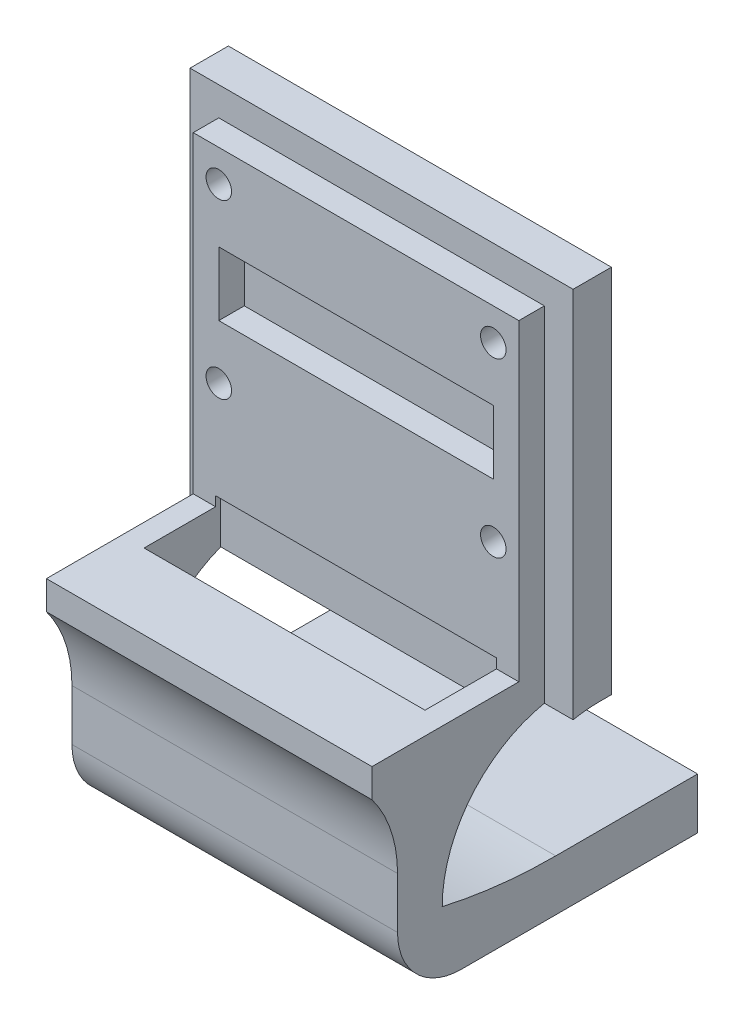
SolidWorks part; units mm, degrees
ref_plane "Alzado" through (0, 0, 0) normal (0, 0, 1) x (1, 0, 0)
ref_plane "Planta" through (0, 0, 0) normal (0, 1, 0) x (1, 0, 0)
ref_plane "Vista lateral" through (0, 0, 0) normal (1, 0, 0) x (0, 0, -1)
sketch "Croquis3" plane through (0, 0, 0) normal (0, 0, 1) x (1, 0, 0)
  line L1 (15, 14.5) -> (-15, 14.5)
  line L2 (15, 14.5) -> (15, -14.5)
  line L3 (15, -14.5) -> (-15, -14.5)
  line L4 (-15, 14.5) -> (-15, -14.5)
  line L5 (15, 14.5) -> (-15, -14.5) construction
  line L6 (15, -14.5) -> (-15, 14.5) construction
  point P0 (0, 0)
  dimension "D1" = 30
  dimension "D2" = 29
extrude "Saliente-Extruir1" add sketch "Croquis3" along normal blind 5
sketch "Croquis5" plane through (0, 0, 5) normal (0, 0, 1) x (1, 0, 0)
  line L0 (15, -14.5) -> (15, 14.5) construction
  line L1 (-15, -14.5) -> (15, -14.5) construction
  line L2 (-15, 14.5) -> (-15, -14.5) construction
  line L3 (15, 14.5) -> (-15, 14.5) construction
  line L4 (15, -14.5) -> (15, 14.5)
  line L5 (-15, -14.5) -> (15, -14.5)
  line L6 (-15, 14.5) -> (-15, -14.5)
  line L7 (15, 14.5) -> (-15, 14.5)
  line L9 (12.75, 12.25) -> (-12.75, 12.25)
  line L10 (12.75, 12.25) -> (12.75, -12.25)
  line L11 (12.75, -12.25) -> (-12.75, -12.25)
  line L12 (-12.75, 12.25) -> (-12.75, -12.25)
  line L13 (12.75, 12.25) -> (-12.75, -12.25) construction
  line L14 (12.75, -12.25) -> (-12.75, 12.25) construction
  point P3 (0, 0)
  dimension "D1" = 25.5
  dimension "D2" = 24.5
extrude "Cortar-Extruir1" cut sketch "Croquis5" against normal blind 2
sketch "Croquis6" plane through (0, 0, 0) normal (0, 0, 1) x (1, 0, 0)
  line L0 (0, 15.8754) -> (0, -15.8754) construction
  line L1 (-12.75, 12.25) -> (-12.75, -12.25) construction
  line L2 (12.75, 12.25) -> (-12.75, 12.25) construction
  line L3 (-10.75, -3.75) -> (10.75, -3.75) construction
  line L4 (10.75, -3.75) -> (10.75, 9.75) construction
  line L5 (10.75, 9.75) -> (-10.75, 9.75) construction
  line L6 (-10.75, 9.75) -> (-10.75, -3.75) construction
  circle A0 centre (-10.75, 9.75) radius 1
  circle A2 centre (-10.75, -3.75) radius 1
  circle A9 centre (10.75, -3.75) radius 1
  circle A10 centre (10.75, 9.75) radius 1
  point P4 (0, 0)
  dimension "D1" = 2
  dimension "D2" = 2
  dimension "D3" = 2.5
  dimension "D4" = 13.5
sketch "Croquis9" plane through (0, 0, 3) normal (0, 0, 1) x (1, 0, 0)
  line L0 (-15, -14.5) -> (15, -14.5) construction
  line L1 (-12.75, -12.25) -> (12.75, -12.25)
  line L2 (-12.75, -12.25) -> (-12.75, -14.5)
  line L3 (-12.75, -14.5) -> (12.75, -14.5)
  line L4 (12.75, -12.25) -> (12.75, -14.5)
  line L5 (12.75, -12.25) -> (12.75, 12.25) construction
extrude "Saliente-Extruir2" add sketch "Croquis9" along normal blind 13.5
sketch "Croquis11" plane through (0, -14.5, 0) normal (0, -1, 0) x (1, 0, 0)
  line L1 (11, 10.6) -> (-11, 10.6)
  line L2 (11, 10.6) -> (11, 4.6)
  line L3 (11, 4.6) -> (-11, 4.6)
  line L4 (-11, 10.6) -> (-11, 4.6)
  line L5 (11, 10.6) -> (-11, 4.6) construction
  line L6 (11, 4.6) -> (-11, 10.6) construction
  line L7 (-15, 3) -> (-12.75, 3) construction
  point P0 (0, 7.6)
  dimension "D1" = 22
  dimension "D2" = 11
  dimension "D3" = 6
  dimension "D4" = 1.6
extrude "Cortar-Extruir3" cut sketch "Croquis11" against normal blind 3
sketch "Croquis12" plane through (0, -14.5, 0) normal (0, -1, 0) x (1, 0, 0)
  line L0 (12.75, 16.5) -> (12.75, 3) construction
  line L1 (12.75, 11) -> (-12.75, 11)
  line L2 (12.75, 11) -> (12.75, 14.5)
  line L3 (12.75, 14.5) -> (-12.75, 14.5)
  line L4 (-12.75, 11) -> (-12.75, 14.5)
  line L5 (-12.75, 16.5) -> (-12.75, 3) construction
  line L7 (-12.75, 16.5) -> (12.75, 16.5) construction
  dimension "D1" = 3.5
  dimension "D2" = 2
extrude "Saliente-Extruir3" add sketch "Croquis12" along normal blind 15
sketch "Croquis13" plane through (0, 0, 11) normal (0, 0, -1) x (-1, 0, 0)
  line L0 (12.75, -29.5) -> (12.75, -14.5) construction
  line L1 (-12.75, -29.5) -> (12.75, -29.5)
  line L2 (-12.75, -29.5) -> (-12.75, -25.5)
  line L3 (-12.75, -25.5) -> (12.75, -25.5)
  line L4 (12.75, -29.5) -> (12.75, -25.5)
  dimension "D1" = 4
extrude "Saliente-Extruir4" add sketch "Croquis13" along normal blind 20
fillet "Redondeo3" radius 5 1 edges at (0, -29.5, 14.5)
sketch "Croquis14" plane through (0, -29.5, 0) normal (0, -1, 0) x (1, 0, 0)
  line L0 (12.75, -9) -> (-12.75, -9) construction
  circle A0 centre (0, -3) radius 1.5
  dimension "D1" = 3
  dimension "D2" = 6
extrude "Cortar-Extruir4" cut sketch "Croquis14" against normal blind 7
fillet "Redondeo5" radius 10 2 edges at (0, -14.5, 14.5) (0, -14.5, 11)
fillet "Redondeo6" radius 40 1 edges at (0, -25.5, 11)
extrude "Cortar-Extruir5" cut sketch "Croquis6" along normal blind 5
sketch "Croquis15" plane through (0, 0, 0) normal (0, 0, -1) x (-1, 0, 0)
  line L1 (-10.75, 12.6368) -> (-13.25, 11.1934)
  line L2 (-13.25, 11.1934) -> (-13.25, 8.3066)
  line L3 (-13.25, 8.3066) -> (-10.75, 6.8632)
  line L4 (-10.75, 6.8632) -> (-8.25, 8.3066)
  line L5 (-8.25, 8.3066) -> (-8.25, 11.1934)
  line L6 (-8.25, 11.1934) -> (-10.75, 12.6368)
  line L7 (10.75, 12.6368) -> (8.25, 11.1934)
  line L8 (8.25, 11.1934) -> (8.25, 8.3066)
  line L9 (8.25, 8.3066) -> (10.75, 6.8632)
  line L10 (10.75, 6.8632) -> (13.25, 8.3066)
  line L11 (13.25, 8.3066) -> (13.25, 11.1934)
  line L12 (13.25, 11.1934) -> (10.75, 12.6368)
  line L13 (10.75, -0.8632) -> (8.25, -2.3066)
  line L14 (8.25, -2.3066) -> (8.25, -5.1934)
  line L15 (8.25, -5.1934) -> (10.75, -6.6368)
  line L16 (10.75, -6.6368) -> (13.25, -5.1934)
  line L17 (13.25, -5.1934) -> (13.25, -2.3066)
  line L18 (13.25, -2.3066) -> (10.75, -0.8632)
  line L19 (-10.75, -0.8632) -> (-13.25, -2.3066)
  line L20 (-13.25, -2.3066) -> (-13.25, -5.1934)
  line L21 (-13.25, -5.1934) -> (-10.75, -6.6368)
  line L22 (-10.75, -6.6368) -> (-8.25, -5.1934)
  line L23 (-8.25, -5.1934) -> (-8.25, -2.3066)
  line L24 (-8.25, -2.3066) -> (-10.75, -0.8632)
  circle A0 centre (-10.75, 9.75) radius 2.5 construction
  circle A1 centre (10.75, 9.75) radius 2.5 construction
  circle A2 centre (10.75, -3.75) radius 2.5 construction
  circle A3 centre (-10.75, -3.75) radius 2.5 construction
  dimension "D1" = 5
extrude "Cortar-Extruir7" cut sketch "Croquis15" against normal blind 2
sketch "Croquis16" plane through (0, 0, 5) normal (0, 0, 1) x (1, 0, 0)
  line L0 (-10.75, 9.75) -> (-10.75, -3.75) construction
  line L1 (-10.75, -3.75) -> (10.75, -3.75) construction
  line L2 (10.75, -3.75) -> (10.75, 9.75) construction
  line L3 (10.75, 9.75) -> (-10.75, 9.75) construction
  line L4 (-10.75, 3) -> (10.75, 3) construction
  line L6 (10.75, 0.5) -> (-10.75, 0.5)
  line L7 (10.75, 0.5) -> (10.75, 5.5)
  line L8 (10.75, 5.5) -> (-10.75, 5.5)
  line L9 (-10.75, 0.5) -> (-10.75, 5.5)
  line L10 (10.75, 0.5) -> (-10.75, 5.5) construction
  line L11 (10.75, 5.5) -> (-10.75, 0.5) construction
  point P10 (0, 3)
  dimension "D1" = 5
extrude "Cortar-Extruir8" cut sketch "Croquis16" against normal blind 2
